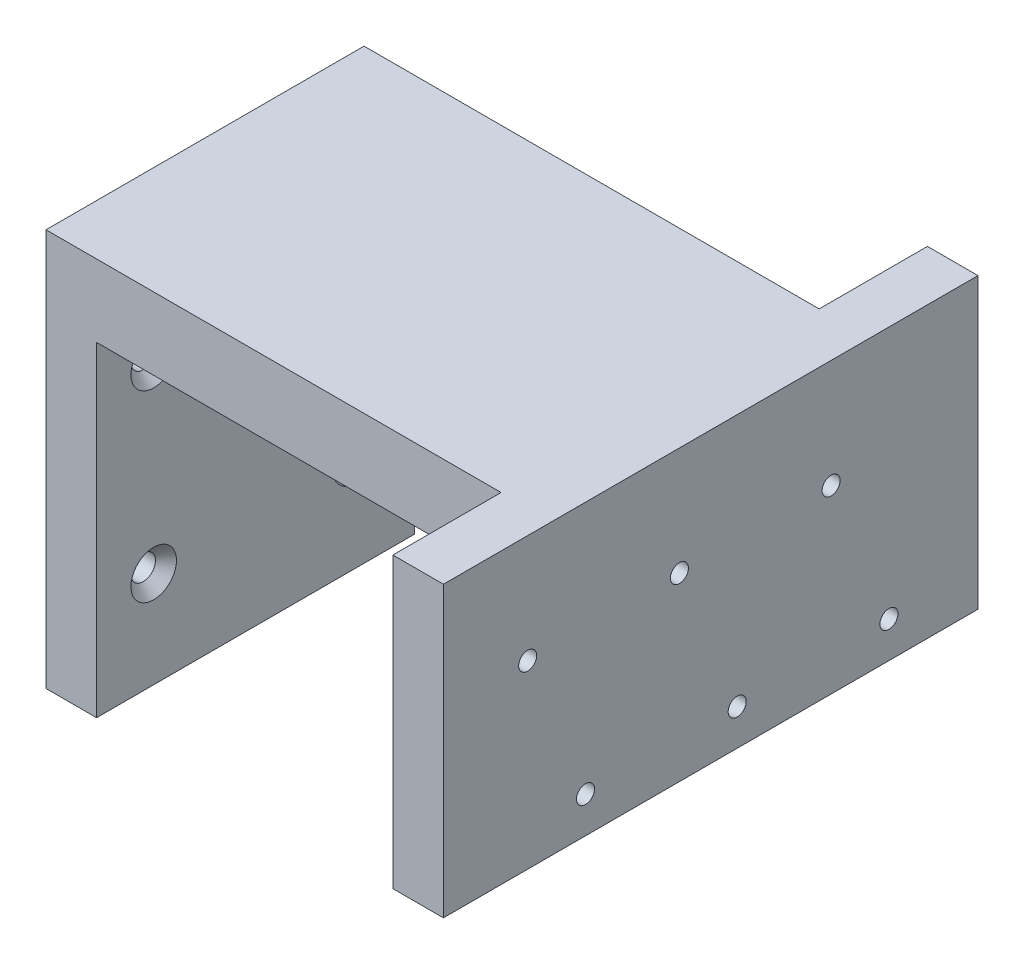
SolidWorks part; units mm, degrees
ref_plane "Front Plane" through (0, 0, 0) normal (0, 0, 1) x (1, 0, 0)
ref_plane "Top Plane" through (0, 0, 0) normal (0, 1, 0) x (1, 0, 0)
ref_plane "Right Plane" through (0, 0, 0) normal (1, 0, 0) x (0, 0, -1)
sketch "Sketch1" plane through (0, 0, 0) normal (0, 0, 1) x (1, 0, 0)
  line L1 (0, 0) -> (70, 0)
  line L2 (0, 0) -> (0, 55)
  line L3 (0, 55) -> (70, 55)
  line L4 (70, 0) -> (70, 55)
  dimension "D1" = 70
  dimension "D2" = 55
extrude "Boss-Extrude1" add sketch "Sketch1" along normal blind 74
sketch "Sketch2" plane through (0, 0, 74) normal (0, 0, 1) x (1, 0, 0)
  line L0 (7, 0) -> (7, 45)
  line L1 (0, 0) -> (70, 0) construction
  line L2 (7, 45) -> (63, 45)
  line L3 (63, 45) -> (63, 15)
  line L4 (60, 0) -> (7, 0)
  line L5 (0, 55) -> (0, 0) construction
  line L6 (70, 0) -> (70, 55) construction
  line L7 (70, 55) -> (0, 55) construction
  line L8 (63, 15) -> (70, 15)
  line L9 (70, 15) -> (70, 0)
  line L10 (70, 0) -> (60, 0)
  dimension "D1" = 7
  dimension "D2" = 7
  dimension "D3" = 10
  dimension "D4" = 15
extrude "Cut-Extrude1" cut sketch "Sketch2" against normal through all both and the other way through all
sketch "Sketch4" plane through (70, 0, 0) normal (1, 0, 0) x (0, 0, -1)
  line L0 (0, 15) -> (-74, 15) construction
  circle A0 centre (-83.3318, 40) radius 1.25
  circle A1 centre (-75.3318, 20) radius 1.25
  circle A2 centre (-62.3318, 40) radius 1.25
  circle A3 centre (-54.3318, 20) radius 1.25
  circle A4 centre (-41.3318, 40) radius 1.25
  circle A5 centre (-33.3318, 20) radius 1.25
  circle A6 centre (-20.3318, 40) radius 1.25
  circle A7 centre (-12.3318, 20) radius 1.25
  dimension "D1" = 2.5
  dimension "D2" = 2.5
  dimension "D5" = 2.5
  dimension "D6" = 2.5
  dimension "D10" = 2.5
  dimension "D11" = 2.5
  dimension "D14" = 2.5
  dimension "D15" = 2.5
  dimension "D3" = 8
  dimension "D4" = 20
  dimension "D7" = 8
  dimension "D8" = 20
  dimension "D9" = 13
  dimension "D12" = 8
  dimension "D13" = 20
  dimension "D16" = 8
  dimension "D17" = 20
  dimension "D18" = 13
  dimension "D19" = 13
  dimension "D20" = 5
  dimension "D21" = 5
  dimension "D22" = 5
  dimension "D23" = 5
extrude "Cut-Extrude4" cut sketch "Sketch4" against normal up to surface (7 mm away) up to face at (63, 30, 37)
sketch "Sketch5" plane through (0, 0, 0) normal (-1, 0, 0) x (0, 0, 1)
  line L0 (0, 27.5) -> (74, 27.5) construction
  line L1 (0, 55) -> (0, 0) construction
  line L2 (74, 55) -> (74, 0) construction
  line L3 (74, 0) -> (0, 0) construction
  line L4 (14.9857, 55) -> (59.0143, 55)
  line L5 (14.9857, 55) -> (14.9857, 0)
  line L6 (14.9857, 0) -> (59.0143, 0)
  line L7 (59.0143, 55) -> (59.0143, 0)
  line L8 (14.9857, 55) -> (59.0143, 0) construction
  line L9 (14.9857, 0) -> (59.0143, 55) construction
  line L11 (0, 55) -> (14.9857, 55)
  line L12 (0, 55) -> (0, 0)
  line L13 (0, 0) -> (14.9857, 0)
  line L14 (14.9857, 55) -> (14.9857, 0)
  line L15 (59.0143, 55) -> (74, 55)
  line L16 (59.0143, 55) -> (59.0143, 0)
  line L17 (59.0143, 0) -> (74, 0)
  line L18 (74, 55) -> (74, 0)
  point P6 (37, 27.5)
  line M2 (0, 55) -> (0, 0)
  line M3 (0, 0) -> (74, 0)
  line M4 (74, 0) -> (74, 55)
  line M5 (74, 55) -> (0, 55)
extrude "Cut-Extrude5" cut sketch "Sketch5" against normal blind 63 contours L5 M5 M2 M3 | L7 M5 M3 M4 region at (0, 27.5, 7.4929) region at (0, 27.5, 66.5071)
sketch "Sketch8" plane through (7, 0, 0) normal (1, 0, 0) x (0, 0, 1)
  line L0 (37.1377, -10.1906) -> (37.1377, -48.2906) construction
  line L3 (16.1827, -26.0393) -> (58.0927, -26.0393) construction
  line L6 (23.1677, -13.3393) -> (23.1677, -38.7393) construction
  line L7 (30.1527, -10.1906) -> (30.1527, -48.2906) construction
  line L8 (44.1227, -10.1906) -> (44.1227, -48.2906) construction
  line L15 (58.0927, -10.1906) -> (16.1827, -10.1906) construction
  line L16 (16.1827, -10.1906) -> (16.1827, -48.2906) construction
  line L17 (16.1827, -48.2906) -> (58.0927, -48.2906) construction
  line L18 (58.0927, -48.2906) -> (58.0927, -10.1906) construction
  circle A0 centre (23.1677, -13.3393) radius 1
  circle A1 centre (51.1077, -13.3393) radius 1
  circle A2 centre (23.1677, -38.7393) radius 1
  circle A3 centre (51.1077, -38.7393) radius 1
  circle A4 centre (37.1377, -29.2406) radius 1
  point P0 (23.1677, -13.3393)
  point P2 (51.1077, -13.3393)
  point P4 (23.1677, -38.7393)
  point P6 (51.1077, -38.7393)
  point P32 (23.1677, -13.3393)
  point P39 (23.1677, -38.7393)
  dimension "D3" = 2
  dimension "D4" = 2
  dimension "D1" = 27.94
  dimension "D2" = 25.4
hole_wizard "CSK for M3 Countersunk Flat Head Screw1" positions "Sketch8" profile "Sketch9" countersink size "M3" standard "ISO"
sketch "Sketch9" plane through (7, 38.7393, 23.1677) normal (0, 1, 0) x (0, 0, -1)
  line L0 (0, 0) -> (0, 11.0215)
  line L1 (0, 11.0215) -> (1.7, 10)
  line L2 (1.7, 10) -> (1.7, 1.45)
  line L3 (1.7, 1.45) -> (3.15, 0)
  line L5 (3.15, 0) -> (0, 0)
  line L6 (-1.7, 1.45) -> (-3.15, 0) construction
  line L10 (0, 11.0215) -> (-1.7, 10) construction
  line L11 (0, -6.35) -> (0, 107.95) construction
  dimension "Hole Dia." = 3.4
  dimension "Hole Depth" = 10
  dimension "Near C'Sink Dia." = 6.3
  dimension "Near C'Sink Angle" = 90
  dimension "Drill Angle" = 118
